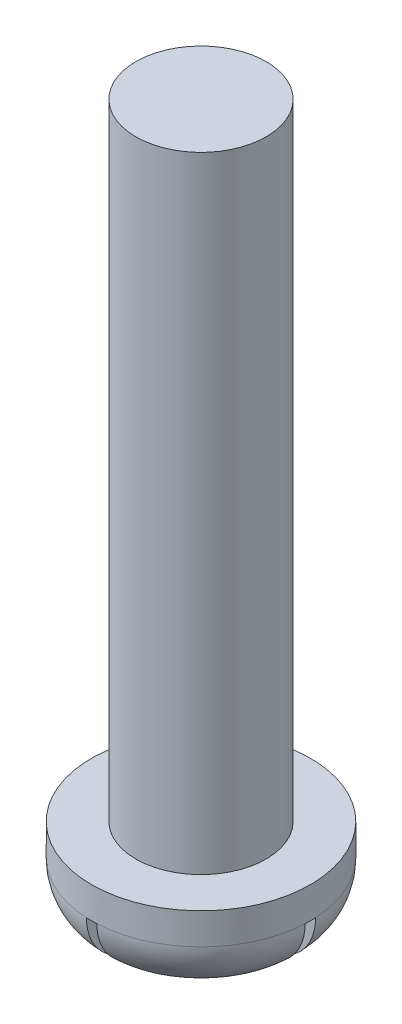
SolidWorks part; units mm, degrees
ref_plane "前视基准面" through (0, 0, 0) normal (0, 0, 1) x (1, 0, 0)
ref_plane "上视基准面" through (0, 0, 0) normal (0, 1, 0) x (1, 0, 0)
ref_plane "右视基准面" through (0, 0, 0) normal (1, 0, 0) x (0, 0, -1)
other "Configuration Table"
sketch "草图1" plane through (0, 0, 0) normal (0, 1, 0) x (1, 0, 0)
  circle A0 centre (0, 0) radius 2.1
  dimension "D1" = 4.2
extrude "凸台-拉伸1" add sketch "草图1" against normal blind 1.6
sketch "草图2" plane through (0, 0, 0) normal (0, 1, 0) x (1, 0, 0)
  circle A0 centre (0, 0) radius 1.25
  dimension "D1" = 2.5
extrude "凸台-拉伸2" add sketch "草图2" along normal blind 12 contours A0
sketch "草图4" plane through (0, -1.6, 0) normal (0, -1, 0) x (1, 0, 0)
  line L0 (-2.1, 0) -> (2.1, 0)
  line L1 (0, 2.1) -> (0, -2.1)
  circle A1 centre (0, 0) radius 2.1 construction
extrude "切除-拉伸-薄壁1" cut sketch "草图4" against normal blind 1 and the other way through all thin thin type mid plane wall 0.2
ref_axis "基准轴1" through (0, 23.8772, 0) along (0, -1, 0)
fillet "圆角1" radius 1 4 edges at (1.4849, -1.6, 1.4849) (-1.4849, -1.6, 1.4849) (-1.4849, -1.6, -1.4849) (1.4849, -1.6, -1.4849)
